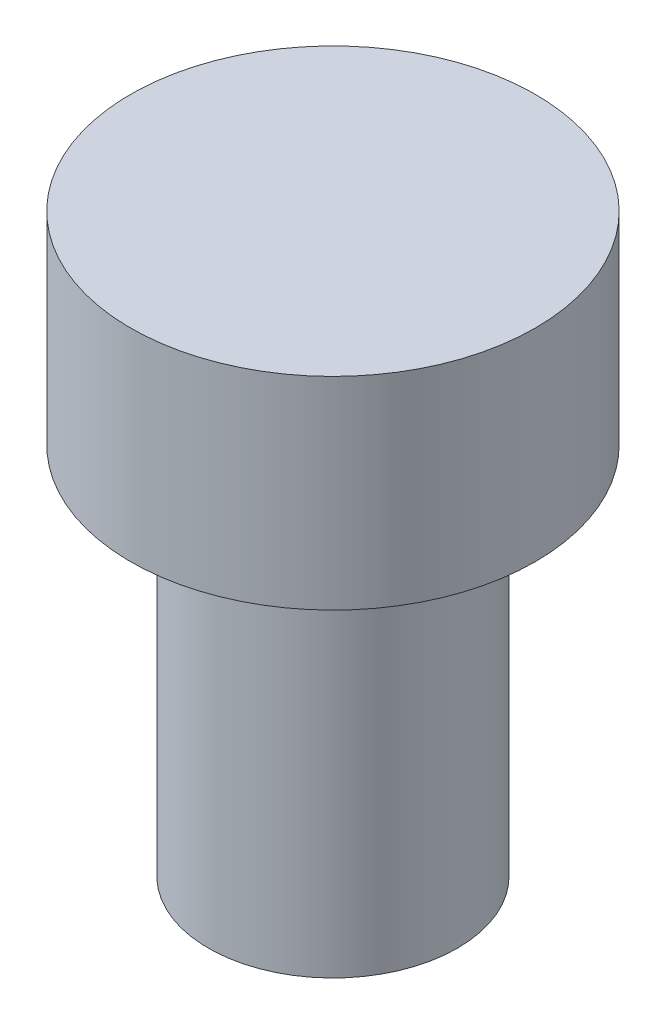
SolidWorks part; units mm, degrees
material "ABS PC"
ref_plane "Front Plane" through (0, 0, 0) normal (0, 0, 1) x (1, 0, 0)
ref_plane "Top Plane" through (0, 0, 0) normal (0, 1, 0) x (1, 0, 0)
ref_plane "Right Plane" through (0, 0, 0) normal (1, 0, 0) x (0, 0, -1)
sketch "Extrude sketch 1" plane through (0, 0, 0) normal (0, 0, 1) x (1, 0, 0)
  circle A0 centre (0, 0) radius 16
  dimension "D1" = 32
extrude "Extrude 1" add sketch "Extrude sketch 1" along normal blind 48 from offset 60 separate body offset against normal yes
move or copy body "Extrude rotate 1" bodies to move or copy 101 copy no rotation origin (0, 0, 0) rotation axis (-1, 0, 0) rotation angle 90
move or copy body "Extrude place 1" bodies to move or copy 102 copy no translate (757.5, 0, 515) parameters "D1"=757.5, "D2"=0, "D3"=515
sketch "Extrude sketch 2" plane through (0, 0, 0) normal (0, 0, 1) x (1, 0, 0)
  circle A0 centre (0, 0) radius 26
  dimension "D1" = 52
extrude "Extrude 2" add sketch "Extrude sketch 2" along normal blind 26 from offset 12 separate body offset against normal yes
move or copy body "Extrude rotate 2" bodies to move or copy 104 copy no rotation origin (0, 0, 0) rotation axis (-1, 0, 0) rotation angle 90
move or copy body "Extrude place 2" bodies to move or copy 105 copy no translate (757.5, 0, 515) parameters "D1"=757.5, "D2"=0, "D3"=515
combine bodies "Combine (weld / assembly of features)" operation type add bodies to combine 103 106
